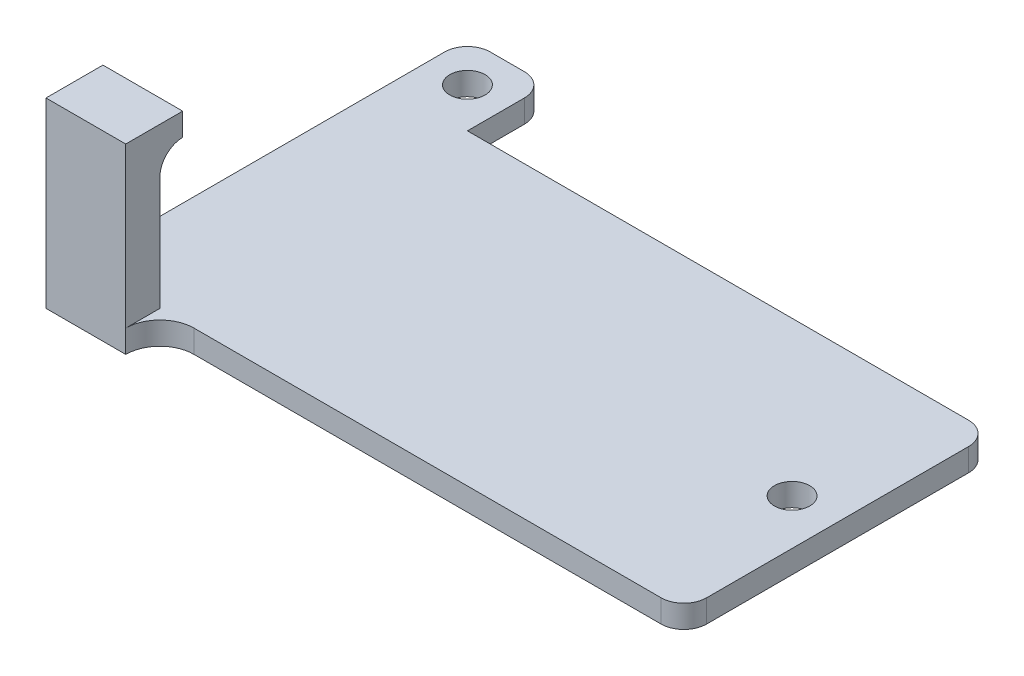
SolidWorks part; units mm, degrees
ref_plane "Plano frontal" through (0, 0, 0) normal (0, 0, 1) x (1, 0, 0)
ref_plane "Plano superior" through (0, 0, 0) normal (0, 1, 0) x (1, 0, 0)
ref_plane "Plano direito" through (0, 0, 0) normal (1, 0, 0) x (0, 0, -1)
sketch "Esboço1" plane through (0, 0, 0) normal (0, 1, 0) x (1, 0, 0)
  line L0 (-26.5, 0) -> (26.5, 0) construction
  line L1 (-26.5, 13.5) -> (26.5, 13.5)
  line L2 (-26.5, 13.5) -> (-26.5, -13.5)
  line L3 (-26.5, -13.5) -> (26.5, -13.5)
  line L4 (26.5, 13.5) -> (26.5, -13.5)
  line L5 (-26.5, 13.5) -> (26.5, -13.5) construction
  line L6 (-26.5, -13.5) -> (26.5, 13.5) construction
  line L8 (-26.5, -13.5) -> (-19.5, -13.5)
  line L9 (-26.5, -13.5) -> (-26.5, -16.5)
  line L10 (-26.5, -16.5) -> (-19.5, -16.5)
  line L11 (-19.5, -13.5) -> (-19.5, -16.5)
  line L12 (-26.5, -13.5) -> (-19.5, -16.5) construction
  line L13 (-26.5, -16.5) -> (-19.5, -13.5) construction
  line L14 (-26.5, 13.5) -> (-19.5, 13.5)
  line L15 (-26.5, 13.5) -> (-26.5, 20.5)
  line L16 (-26.5, 20.5) -> (-19.5, 20.5)
  line L17 (-19.5, 13.5) -> (-19.5, 20.5)
  line L18 (-26.5, 13.5) -> (-19.5, 20.5) construction
  line L19 (-26.5, 20.5) -> (-19.5, 13.5) construction
  circle A0 centre (-23, 17) radius 1.55
  point P0 (0, 0)
  point P6 (-23, -15)
  point P9 (0, 0)
  point P18 (-23, 17)
  dimension "D5" = 3.1
  dimension "D1" = 27
  dimension "D2" = 53
  dimension "D3" = 7
  dimension "D4" = 3
extrude "Ressalto-extrusão1" add sketch "Esboço1" against normal blind 2 contours L11 L3 L9 L10 | L4 L1 L2 L3 | L1 L17 L16 L15 A0 region at (-26.401, 0, -17) region at (0, 0, 0) region at (-23, 0, 15)
sketch "Esboço2" plane through (0, 0, 0) normal (0, 1, 0) x (1, 0, 0)
  line L1 (-26.5, -16.5) -> (-19.5, -16.5)
  line L2 (-26.5, -16.5) -> (-26.5, -13.5)
  line L3 (-26.5, -13.5) -> (-19.5, -13.5)
  line L4 (-19.5, -16.5) -> (-19.5, -13.5)
  line L5 (-26.5, -16.5) -> (-19.5, -13.5) construction
  line L6 (-26.5, -13.5) -> (-19.5, -16.5) construction
  point P4 (-23, -15)
extrude "Ressalto-extrusão2" add sketch "Esboço2" along normal blind 14
sketch "Esboço3" plane through (0, 0, 13.5) normal (0, 0, -1) x (-1, 0, 0)
  line L0 (26.5, 14) -> (26.5, 0) construction
  line L1 (19.5, 14) -> (26.5, 14)
  line L2 (19.5, 14) -> (19.5, 12)
  line L3 (19.5, 12) -> (26.5, 12)
  line L4 (26.5, 14) -> (26.5, 12)
  line L5 (19.5, 14) -> (26.5, 12) construction
  line L6 (19.5, 12) -> (26.5, 14) construction
  point P4 (23, 13)
  dimension "D1" = 2
extrude "Ressalto-extrusão3" add sketch "Esboço3" along normal blind 2
fillet "Filete1" radius 2 1 edges at (-23, 12, 13.5)
sketch "Esboço4" plane through (0, 0, 0) normal (0, 1, 0) x (1, 0, 0)
  line L0 (0, 0) -> (26.5, 0) construction
  line L1 (26.5, 13.5) -> (26.5, -13.5) construction
  circle A0 centre (22.5, 0) radius 1.55
  dimension "D1" = 3.1
  dimension "D2" = 4
fillet "Filete2" radius 3 1 edges at (-19.5, -1, 13.5)
extrude "Corte-extrusão1" cut sketch "Esboço4" against normal blind 2
fillet "Filete3" radius 2 4 edges at (26.5, -1, 13.5) (26.5, -1, -13.5) (-26.5, -1, -20.5) (-19.5, -1, -20.5)
